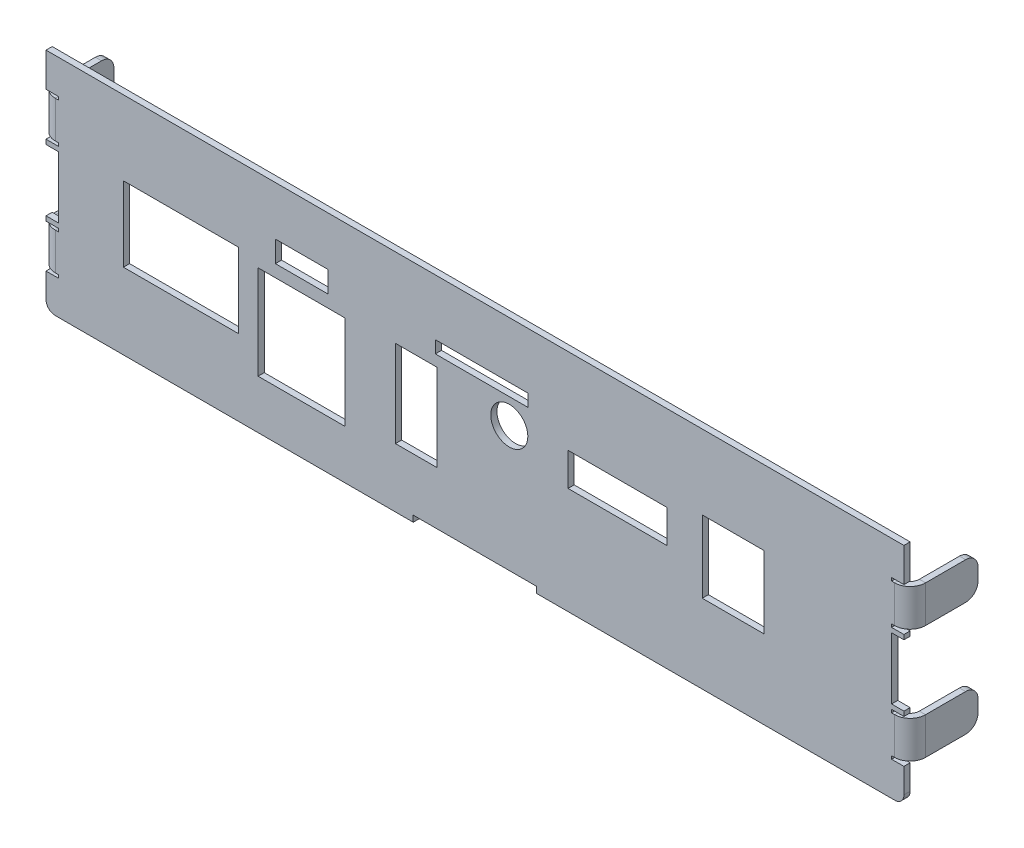
SolidWorks part; units mm, degrees
note: The reader was unsure of these and kept them because the rebuilt part matched: flange length of "Edge-Flange1", "Edge-Flange2".
material "Galvanized Steel"
ref_plane "Front Plane" through (0, 0, 0) normal (0, 0, 1) x (1, 0, 0)
ref_plane "Top Plane" through (0, 0, 0) normal (0, 1, 0) x (1, 0, 0)
ref_plane "Right Plane" through (0, 0, 0) normal (1, 0, 0) x (0, 0, -1)
sketch "Sketch1" plane through (0, 0, 0) normal (0, 0, 1) x (1, 0, 0)
  line L0 (-68.571, 18.25) -> (70.429, 18.25)
  line L1 (-68.571, 18.25) -> (-68.571, -18.25)
  line L2 (-68.571, -18.25) -> (70.429, -18.25)
  line L3 (70.429, 18.25) -> (70.429, -18.25)
  line L4 (-68.571, 0) -> (68.571, 0) construction
  line L5 (0.929, 18.25) -> (0.929, -18.25) construction
  point P8 (0, 0)
  dimension "D1" = 139
  dimension "D2" = 36.5
base flange "Base-Flange1" sketch "Sketch1" thickness 1 reverse thickness direction no parameters "D1"=1
edge flange "Edge-Flange1" sketch "Sketch11" flange profiles "Sketch11", "Sketch13" flange angle 90 flange length 10 flange position material outside bend radius 1.5 thickness 1 relief rectangular parameters "D6"=10, "D8"=1
sketch "Sketch11" plane through (-68.571, 0, -1) normal (1, 0, 0) x (0, -1, 0)
  line L1 (18.25, 0) -> (-18.25, 0) construction
  line L2 (-12.25, 0) -> (-12.25, 8)
  line L3 (-10.25, 10) -> (-8.25, 10)
  line L4 (-6.25, 8) -> (-6.25, 0)
  line L5 (-6.25, 0) -> (-12.25, 0)
  line L6 (-18.25, 0) -> (-18.25, -1) construction
  arc A0 (-8.25, 10) -> (-6.25, 8) centre (-8.25, 8) cw
  arc A1 (-12.25, 8) -> (-10.25, 10) centre (-10.25, 8) cw
  point P10 (-18.25, -0.5)
  point P12 (-6.25, 10)
  point P15 (-12.25, 10)
  dimension "D4" = 2
  dimension "D1" = 6
  dimension "D2" = 6
  dimension "D3" = 10
sketch "Sketch13" plane through (70.429, 0, -1) normal (-1, 0, 0) x (0, 1, 0)
  line L0 (18.25, 0) -> (-18.25, 0) construction
  line L1 (12.25, 0) -> (6.25, 0)
  line L2 (12.25, 0) -> (12.25, 8)
  line L3 (10.25, 10) -> (8.25, 10)
  line L4 (6.25, 8) -> (6.25, 0)
  line L5 (18.25, 0) -> (18.25, -1) construction
  arc A0 (12.25, 8) -> (10.25, 10) centre (10.25, 8) ccw
  arc A1 (8.25, 10) -> (6.25, 8) centre (8.25, 8) ccw
  point P10 (12.25, 10)
  point P13 (6.25, 10)
  dimension "D4" = 2
  dimension "D1" = 6
  dimension "D2" = 6
  dimension "D3" = 10
bend "EdgeBend1" bend radius 1.5 bend angle 90 parameters "D5"=1
bend "EdgeBend2" bend radius 1.5 bend angle 90 parameters "D5"=3
edge flange "Edge-Flange2" sketch "Sketch18" flange profiles "Sketch18", "Sketch19" flange angle 90 flange length 10 flange position material outside bend radius 1.5 thickness 1 relief rectangular parameters "D6"=10, "D8"=1
sketch "Sketch18" plane through (70.429, 0, -1) normal (1, 0, 0) x (0, -1, 0)
  line L0 (18.25, 0) -> (-5.75, 0) construction
  line L1 (12.25, 0) -> (6.25, 0)
  line L2 (6.25, 0) -> (6.25, 8)
  line L3 (8.25, 10) -> (10.25, 10)
  line L4 (12.25, 8) -> (12.25, 0)
  line L5 (18.25, 0) -> (18.25, -1) construction
  arc A0 (10.25, 10) -> (12.25, 8) centre (10.25, 8) cw
  arc A1 (6.25, 8) -> (8.25, 10) centre (8.25, 8) cw
  point P6 (18.25, -0.5)
  point P11 (12.25, 10)
  point P14 (6.25, 10)
  dimension "D4" = 2
  dimension "D1" = 6
  dimension "D2" = 6
  dimension "D3" = 10
sketch "Sketch19" plane through (-68.571, 0, -1) normal (-1, 0, 0) x (0, 1, 0)
  line L0 (5.75, 0) -> (-18.25, 0) construction
  line L1 (-6.25, 0) -> (-12.25, 0)
  line L2 (-12.25, 0) -> (-12.25, 8)
  line L3 (-10.25, 10) -> (-8.25, 10)
  line L4 (-6.25, 8) -> (-6.25, 0)
  line L5 (-18.25, 0) -> (-18.25, -1) construction
  arc A0 (-8.25, 10) -> (-6.25, 8) centre (-8.25, 8) cw
  arc A1 (-12.25, 8) -> (-10.25, 10) centre (-10.25, 8) cw
  point P8 (-18.25, -0.5)
  point P11 (-6.25, 10)
  point P14 (-12.25, 10)
  dimension "D4" = 2
  dimension "D1" = 6
  dimension "D2" = 6
  dimension "D3" = 10
bend "EdgeBend3" bend radius 1.5 bend angle 90 parameters "D5"=4
bend "EdgeBend4" bend radius 1.5 bend angle 90 parameters "D5"=5
sketch "Sketch20" plane through (0, 0, -1) normal (0, 0, -1) x (-1, 0, 0)
  line L0 (68.571, -18.25) -> (-70.429, -18.25) construction
  line L1 (-10.929, -18.25) -> (9.071, -18.25)
  line L2 (-10.929, -18.25) -> (-10.929, -17.25)
  line L3 (-10.929, -17.25) -> (9.071, -17.25)
  line L4 (9.071, -18.25) -> (9.071, -17.25)
  line L5 (-70.429, -18.25) -> (-70.429, -12.75) construction
  line L6 (-70.429, -5.75) -> (-70.429, 5.75) construction
  line L7 (-70.429, 5) -> (-68.429, 5)
  line L8 (-70.429, 5) -> (-70.429, -5)
  line L9 (-70.429, -5) -> (-68.429, -5)
  line L10 (-68.429, 5) -> (-68.429, -5)
  line L11 (68.571, 5.75) -> (68.571, -5.75) construction
  line L12 (68.571, 5) -> (66.571, 5)
  line L13 (68.571, 5) -> (68.571, -5)
  line L14 (68.571, -5) -> (66.571, -5)
  line L15 (66.571, 5) -> (66.571, -5)
  dimension "D1" = 1
  dimension "D2" = 59.5
  dimension "D3" = 20
  dimension "D4" = 10
  dimension "D5" = 2
  dimension "D6" = 13.25
  dimension "D7" = 2
  dimension "D8" = 10
  dimension "D9" = 13.25
extrude "Cut-Extrude1" cut sketch "Sketch20" against normal blind 10 normal cut yes
fillet "Fillet1" radius 1.5 2 edges at (70.429, -18.25, -0.5) (-68.571, -18.25, -0.5)
sketch "Sketch21" plane through (0, 0, 0) normal (0, 0, 1) x (1, 0, 0)
  line L0 (9.5101, 9.1608) -> (9.5101, 7.1608)
  line L1 (-55.5291, 5.6849) -> (-37.9099, 5.6849)
  line L2 (-55.5291, 5.6849) -> (-55.5291, -5.4402)
  line L3 (-55.5291, -5.4402) -> (-37.9099, -5.4402)
  line L4 (-37.9099, 5.6849) -> (-37.9099, -5.4402)
  line L5 (-33.7099, 4.3845) -> (-20.6099, 4.3845)
  line L6 (-33.7099, 4.3845) -> (-33.7099, -9.825)
  line L7 (-33.7099, -9.825) -> (-20.6099, -9.825)
  line L8 (-20.6099, 4.3845) -> (-20.6099, -9.825)
  line L9 (-11.4501, 4.9205) -> (-5.7001, 4.9205)
  line L10 (-11.4501, 4.9205) -> (-11.4501, -8.1549)
  line L11 (-11.4501, -8.1549) -> (-5.7001, -8.1549)
  line L12 (-5.7001, 4.9205) -> (-5.7001, -8.1549)
  line L13 (-5.4899, 9.1608) -> (9.5101, 9.1608)
  line L14 (-5.4899, 9.1608) -> (-5.4899, 7.1608)
  line L15 (-5.4899, 7.1608) -> (9.5101, 7.1608)
  line L17 (16.5066, 3.8851) -> (31.5066, 3.8851)
  line L18 (16.5066, 3.8851) -> (16.5066, -0.4649)
  line L19 (16.5066, -0.4649) -> (31.5066, -0.4649)
  line L20 (31.5066, 3.8851) -> (31.5066, -0.4649)
  point P34 (-5.4899, 8.1608)
  dimension "D1" = 2
  dimension "D4" = 15
extrude "Cut-Extrude2" cut sketch "Sketch21" against normal blind 10 normal cut yes
sketch "Sketch22" plane through (0, 0, 0) normal (0, 0, 1) x (1, 0, 0)
  line L22 (31.5066, -0.4649) -> (31.5066, 3.8851) construction
  line L23 (16.5066, -0.4649) -> (31.5066, -0.4649) construction
  line L24 (16.5066, 3.8851) -> (16.5066, -0.4649) construction
  line L25 (31.5066, 3.8851) -> (16.5066, 3.8851) construction
  line L26 (-5.7001, 4.9205) -> (-11.4501, 4.9205) construction
  line L27 (-5.7001, -8.1549) -> (-5.7001, 4.9205) construction
  line L28 (-11.4501, -8.1549) -> (-5.7001, -8.1549) construction
  line L29 (-11.4501, 4.9205) -> (-11.4501, -8.1549) construction
  line L30 (-20.6099, -9.825) -> (-20.6099, 4.3845) construction
  line L31 (-33.7099, -9.825) -> (-20.6099, -9.825) construction
  line L32 (-20.6099, 4.3845) -> (-33.7099, 4.3845) construction
  line L33 (-33.7099, 4.3845) -> (-33.7099, -9.825) construction
  line L34 (-37.9099, -5.4402) -> (-37.9099, 5.6849) construction
  line L35 (-55.5291, -5.4402) -> (-37.9099, -5.4402) construction
  line L36 (-55.5291, 5.6849) -> (-55.5291, -5.4402) construction
  line L37 (-37.9099, 5.6849) -> (-55.5291, 5.6849) construction
  line L42 (31.5066, -0.4649) -> (31.5066, 3.8851)
  line L43 (16.5066, -0.4649) -> (31.5066, -0.4649)
  line L44 (16.5066, 3.8851) -> (16.5066, -0.4649)
  line L45 (31.5066, 3.8851) -> (16.5066, 3.8851)
  line L46 (-5.7001, 4.9205) -> (-11.4501, 4.9205)
  line L47 (-5.7001, -8.1549) -> (-5.7001, 4.9205)
  line L48 (-11.4501, -8.1549) -> (-5.7001, -8.1549)
  line L49 (-11.4501, 4.9205) -> (-11.4501, -8.1549)
  line L50 (-20.6099, -9.825) -> (-20.6099, 4.3845)
  line L51 (-33.7099, -9.825) -> (-20.6099, -9.825)
  line L52 (-20.6099, 4.3845) -> (-33.7099, 4.3845)
  line L53 (-33.7099, 4.3845) -> (-33.7099, -9.825)
  line L54 (-37.9099, -5.4402) -> (-37.9099, 5.6849)
  line L55 (-55.5291, -5.4402) -> (-37.9099, -5.4402)
  line L56 (-55.5291, 5.6849) -> (-55.5291, -5.4402)
  line L57 (-37.9099, 5.6849) -> (-55.5291, 5.6849)
  line L62 (-31.4101, 10.3161) -> (-31.4101, 6.8661)
  line L63 (-31.4101, 6.8661) -> (-22.9099, 6.8661)
  line L64 (-22.9099, 6.8661) -> (-22.9099, 10.3161)
  line L65 (-22.9099, 10.3161) -> (-31.4101, 10.3161)
  line L66 (-31.4101, 10.3161) -> (-31.4101, 6.8661)
  line L67 (-31.4101, 6.8661) -> (-22.9099, 6.8661)
  line L68 (-22.9099, 6.8661) -> (-22.9099, 10.3161)
  line L69 (-22.9099, 10.3161) -> (-31.4101, 10.3161)
  line L96 (37.7551, 6.1982) -> (37.7551, -5.4998)
  line L101 (37.7551, -5.4998) -> (47.7551, -5.4998)
  line L102 (47.7551, 6.1982) -> (47.7551, -5.4998)
  line L103 (37.7551, 6.1982) -> (47.7551, 6.1982)
  line L128 (-37.4099, -5.9402) -> (-37.4099, 6.1849)
  line L129 (-56.0291, -5.9402) -> (-37.4099, -5.9402)
  line L130 (-37.4099, 6.1849) -> (-56.0291, 6.1849)
  line L131 (-56.0291, 6.1849) -> (-56.0291, -5.9402)
  line L132 (-37.4099, -5.9402) -> (-37.4099, 6.1849)
  line L133 (-56.0291, -5.9402) -> (-37.4099, -5.9402)
  line L134 (-37.4099, 6.1849) -> (-56.0291, 6.1849)
  line L135 (-56.0291, 6.1849) -> (-56.0291, -5.9402)
  line L226 (-20.1099, -10.325) -> (-20.1099, 4.8845)
  line L227 (-34.2099, -10.325) -> (-20.1099, -10.325)
  line L228 (-34.2099, 4.8845) -> (-34.2099, -10.325)
  line L229 (-20.1099, 4.8845) -> (-34.2099, 4.8845)
  line L230 (-20.1099, -10.325) -> (-20.1099, 4.8845)
  line L231 (-34.2099, -10.325) -> (-20.1099, -10.325)
  line L232 (-34.2099, 4.8845) -> (-34.2099, -10.325)
  line L233 (-20.1099, 4.8845) -> (-34.2099, 4.8845)
  line L283 (-5.2001, -8.6549) -> (-5.2001, 5.4205)
  line L284 (-11.9501, -8.6549) -> (-5.2001, -8.6549)
  line L285 (-11.9501, 5.4205) -> (-11.9501, -8.6549)
  line L286 (-5.2001, 5.4205) -> (-11.9501, 5.4205)
  line L287 (-5.2001, -8.6549) -> (-5.2001, 5.4205)
  line L288 (-11.9501, -8.6549) -> (-5.2001, -8.6549)
  line L289 (-11.9501, 5.4205) -> (-11.9501, -8.6549)
  line L290 (-5.2001, 5.4205) -> (-11.9501, 5.4205)
  line L310 (32.0066, -0.9649) -> (32.0066, 4.3851)
  line L311 (16.0066, -0.9649) -> (32.0066, -0.9649)
  line L312 (16.0066, 4.3851) -> (16.0066, -0.9649)
  line L313 (32.0066, 4.3851) -> (16.0066, 4.3851)
  line L314 (32.0066, -0.9649) -> (32.0066, 4.3851)
  line L315 (16.0066, -0.9649) -> (32.0066, -0.9649)
  line L316 (16.0066, 4.3851) -> (16.0066, -0.9649)
  line L317 (32.0066, 4.3851) -> (16.0066, 4.3851)
  circle A0 centre (6.4902, 3.085) radius 3
  dimension "D1" = 0.5
  dimension "D2" = 0.5
  dimension "D3" = 0.5
  dimension "D4" = 0.5
  dimension "D5" = 0.5
extrude "Cut-Extrude3" cut sketch "Sketch22" against normal blind 10 normal cut yes
sketch "Bend-Lines1" [suppressed] plane through (0, 0, 0) normal (0, 1, 0) x (1, 0, 0)
sketch "Bounding-Box1" [suppressed] plane through (0, 0, 0) normal (0, 1, 0) x (1, 0, 0)
sheet metal parameters "Sheet-Metal1" thickness 1 parameters "D1"=1
flat pattern "Flat-Pattern1" [suppressed]
sketch "Bend-Lines2" plane through (0, 0, 0) normal (0, 1, 0) x (1, 0, 0)
sketch3d "Bounding-Box2" [suppressed]
  line L0 (-68.571, -18.25, 0) -> (69.429, -18.25, 0) construction
  line L1 (-68.571, 18.25, 0) -> (69.429, 18.25, 0) construction
  line L2 (-68.571, -18.25, 0) -> (-68.571, 18.25, 0) construction
  line L3 (69.429, -18.25, 0) -> (69.429, 18.25, 0) construction
sheet metal parameters "Sheet-Metal3" thickness 1 parameters "D1"=1
flat pattern "Flat-Pattern1"
sketch "Bend-Lines2" plane through (0, 0, 0) normal (0, 0, 1) x (1, 0, 0)
  line L0 (-68.8564, 12.25) -> (-68.8564, 6.25) construction
  line L1 (-68.8564, 12.25) -> (-68.8564, 6.25) construction
  line L2 (69.7144, 6.25) -> (69.7144, 12.25) construction
  line L3 (69.7144, 6.25) -> (69.7144, 12.25) construction
sketch3d "Bounding-Box2" [suppressed]
  line L0 (-79.1418, -18.25, 0) -> (79.9998, -18.25, 0) construction
  line L1 (-79.1418, 18.25, 0) -> (79.9998, 18.25, 0) construction
  line L2 (-79.1418, -18.25, 0) -> (-79.1418, 18.25, 0) construction
  line L3 (79.9998, -18.25, 0) -> (79.9998, 18.25, 0) construction
bend of the flat pattern "Flatten-<EdgeBend1>1"
bend of the flat pattern "Flatten-<EdgeBend2>1"
sheet metal parameters "Sheet-Metal4" thickness 1 parameters "D1"=1
flat pattern "Flat-Pattern1"
sketch "Bend-Lines2" plane through (0, 0, 0) normal (0, 0, 1) x (1, 0, 0)
  line L0 (-68.8564, 12.25) -> (-68.8564, 6.25) construction
  line L1 (-68.8564, 12.25) -> (-68.8564, 6.25) construction
  line L2 (69.7144, 6.25) -> (69.7144, 12.25) construction
  line L3 (69.7144, 6.25) -> (69.7144, 12.25) construction
  line L4 (-68.7491, -6.25) -> (-68.7491, -12.25) construction
  line L5 (69.6071, -12.25) -> (69.6071, -6.25) construction
  line L6 (-68.7491, -6.25) -> (-68.7491, -12.25) construction
  line L7 (69.6071, -12.25) -> (69.6071, -6.25) construction
sketch3d "Bounding-Box2" [suppressed]
  line L0 (-79.1418, 18.2501, 0) -> (79.9998, 18.25, 0) construction
  line L1 (-79.1418, -18.2499, 0) -> (79.9998, -18.25, 0) construction
  line L2 (-79.1418, 18.2501, 0) -> (-79.1418, -18.2499, 0) construction
  line L3 (79.9998, 18.25, 0) -> (79.9998, -18.25, 0) construction
bend of the flat pattern "Flatten-<EdgeBend1>1"
bend of the flat pattern "Flatten-<EdgeBend2>1"
bend of the flat pattern "Flatten-<EdgeBend3>1"
bend of the flat pattern "Flatten-<EdgeBend4>1"
sheet metal parameters "Sheet-Metal5" thickness 1 parameters "D1"=1
flat pattern "Flat-Pattern1"
sketch "Bend-Lines2" plane through (0, 0, 0) normal (0, 0, 1) x (1, 0, 0)
  line L0 (-68.8564, 12.25) -> (-68.8564, 6.25) construction
  line L1 (-68.8564, 12.25) -> (-68.8564, 6.25) construction
  line L2 (69.7144, 6.25) -> (69.7144, 12.25) construction
  line L3 (69.7144, 6.25) -> (69.7144, 12.25) construction
  line L4 (-68.7491, -6.25) -> (-68.7491, -12.25) construction
  line L5 (69.6071, -12.25) -> (69.6071, -6.25) construction
  line L6 (-68.7491, -6.25) -> (-68.7491, -12.25) construction
  line L7 (69.6071, -12.25) -> (69.6071, -6.25) construction
sketch3d "Bounding-Box2" [suppressed]
  line L0 (-79.1418, -18.25, 0) -> (79.9998, -18.25, 0) construction
  line L1 (-79.1418, 18.25, 0) -> (79.9998, 18.25, 0) construction
  line L2 (-79.1418, -18.25, 0) -> (-79.1418, 18.25, 0) construction
  line L3 (79.9998, -18.25, 0) -> (79.9998, 18.25, 0) construction
bend of the flat pattern "Flatten-<EdgeBend1>1"
bend of the flat pattern "Flatten-<EdgeBend2>1"
bend of the flat pattern "Flatten-<EdgeBend3>1"
bend of the flat pattern "Flatten-<EdgeBend4>1"
sheet metal parameters "Sheet-Metal7" thickness 1 parameters "D1"=1
flat pattern "Flat-Pattern1"
sketch "Bend-Lines2" plane through (0, 0, 0) normal (0, 0, 1) x (1, 0, 0)
  line L0 (-68.8564, 12.25) -> (-68.8564, 6.25) construction
  line L1 (-68.8564, 12.25) -> (-68.8564, 6.25) construction
  line L2 (69.7144, 6.25) -> (69.7144, 12.25) construction
  line L3 (69.7144, 6.25) -> (69.7144, 12.25) construction
  line L4 (-68.7491, -6.25) -> (-68.7491, -12.25) construction
  line L5 (69.6071, -12.25) -> (69.6071, -6.25) construction
  line L6 (-68.7491, -6.25) -> (-68.7491, -12.25) construction
  line L7 (69.6071, -12.25) -> (69.6071, -6.25) construction
sketch3d "Bounding-Box2" [suppressed]
  line L0 (-79.1418, -18.25, 0) -> (79.9998, -18.25, 0) construction
  line L1 (-79.1418, 18.25, 0) -> (79.9998, 18.25, 0) construction
  line L2 (-79.1418, -18.25, 0) -> (-79.1418, 18.25, 0) construction
  line L3 (79.9998, -18.25, 0) -> (79.9998, 18.25, 0) construction
bend of the flat pattern "Flatten-<EdgeBend1>1"
bend of the flat pattern "Flatten-<EdgeBend2>1"
bend of the flat pattern "Flatten-<EdgeBend3>1"
bend of the flat pattern "Flatten-<EdgeBend4>1"
sheet metal parameters "Sheet-Metal8" thickness 1 parameters "D1"=1
flat pattern "Flat-Pattern1"
sketch "Bend-Lines2" plane through (0, 0, 0) normal (0, 0, 1) x (1, 0, 0)
  line L0 (-68.6418, 12.25) -> (-68.6418, 6.25) construction
  line L1 (-68.6418, 12.25) -> (-68.6418, 6.25) construction
  line L2 (70.4998, 6.25) -> (70.4998, 12.25) construction
  line L3 (70.4998, 6.25) -> (70.4998, 12.25) construction
  line L4 (-68.6418, -6.25) -> (-68.6418, -12.25) construction
  line L5 (70.4998, -12.25) -> (70.4998, -6.25) construction
  line L6 (-68.6418, -6.25) -> (-68.6418, -12.25) construction
  line L7 (70.4998, -12.25) -> (70.4998, -6.25) construction
sketch3d "Bounding-Box2" [suppressed]
  line L0 (-78.7126, 18.2501, 0) -> (80.5706, 18.25, 0) construction
  line L1 (-78.7126, -18.2499, 0) -> (80.5706, -18.25, 0) construction
  line L2 (-78.7126, 18.2501, 0) -> (-78.7126, -18.2499, 0) construction
  line L3 (80.5706, 18.25, 0) -> (80.5706, -18.25, 0) construction
bend of the flat pattern "Flatten-<EdgeBend1>1"
bend of the flat pattern "Flatten-<EdgeBend2>1"
bend of the flat pattern "Flatten-<EdgeBend3>1"
bend of the flat pattern "Flatten-<EdgeBend4>1"
